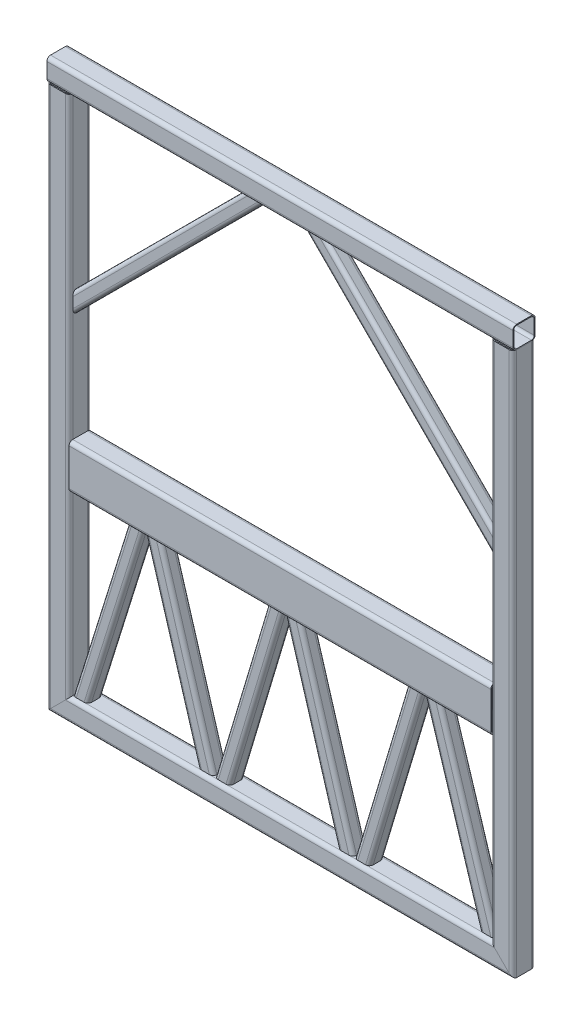
SolidWorks part; units mm, degrees
other "Weld Folder"
material "Plain Carbon Steel"
ref_plane "Front Plane" through (0, 0, 0) normal (0, 0, 1) x (1, 0, 0)
ref_plane "Top Plane" through (0, 0, 0) normal (0, 1, 0) x (1, 0, 0)
ref_plane "Right Plane" through (0, 0, 0) normal (1, 0, 0) x (0, 0, -1)
sketch "Sketch1" plane through (0, 0, 0) normal (0, 0, 1) x (1, 0, 0)
  line L0 (0, 0) -> (1524, 0)
  line L1 (1460.5, 38.1) -> (1270, 647.7)
  line L2 (311.15, 647.7) -> (493.7125, 38.1)
  line L3 (550.8625, 38.1) -> (733.425, 647.7)
  line L4 (1212.85, 647.7) -> (1030.2875, 38.1)
  line L5 (38.1, 1131.8875) -> (522.2875, 1131.8875) construction
  line L6 (254, 647.7) -> (63.5, 38.1)
  line L7 (0, 647.7) -> (1524, 647.7) construction
  line L8 (1524, 0) -> (1524, 1828.8)
  line L9 (1524, 1828.8) -> (0, 1828.8)
  line L10 (0, 1828.8) -> (0, 0)
  line L11 (38.1, 647.7) -> (38.1, 38.1) construction
  line L12 (38.1, 38.1) -> (1485.9, 38.1) construction
  line L13 (1485.9, 38.1) -> (1485.9, 647.7) construction
  line L14 (1485.9, 38.1) -> (1524, 38.1) construction
  line L15 (38.1, 38.1) -> (0, 38.1) construction
  line L16 (38.1, 38.1) -> (38.1, 0) construction
  line L17 (38.1, 38.1) -> (63.5, 38.1) construction
  line L18 (1485.9, 38.1) -> (1460.5, 38.1) construction
  line L19 (762, 647.7) -> (762, 0) construction
  line L20 (0, 723.9) -> (1524, 723.9)
  line L21 (790.575, 647.7) -> (973.1375, 38.1)
  line L22 (522.2875, 1131.8875) -> (1001.7125, 1131.8875) construction
  line L23 (1001.7125, 1131.8875) -> (1485.9, 1131.8875) construction
  line L24 (311.15, 647.7) -> (733.425, 647.7) construction
  line L25 (522.2875, 1131.8875) -> (522.2875, 647.7) construction
  line L26 (1001.7125, 1131.8875) -> (1001.7125, 647.7) construction
  dimension "D1" = 1524
  dimension "D2" = 76.2
  dimension "D3" = 1828.8
  dimension "D4" = 38.1
  dimension "D5" = 25.4
  dimension "D6" = 1016
  dimension "D7" = 723.9
  dimension "D8" = 57.15
  dimension "D9" = 57.15
  dimension "D10" = 57.15
  dimension "D11" = 57.15
  dimension "D12" = 57.15
ref_plane "Plane5" through (1524, 0, 0) normal (1, 0, 0) x (0, 0, -1)
other "Vertical Members"
ref_plane "Plane7" through (0, 1828.8, 0) normal (0, -1, 0) x (1, 0, 0)
sketch "Sketch111" plane through (0, 1828.8, 0) normal (0, -1, 0) x (1, 0, 0)
  line L0 (-25.4, -34.925) -> (25.4, -34.925)
  line L1 (-34.925, -25.4) -> (-34.925, 25.4)
  line L2 (25.4, 34.925) -> (-25.4, 34.925)
  line L3 (34.925, 25.4) -> (34.925, -25.4)
  line L4 (-25.4, -38.1) -> (25.4, -38.1)
  line L5 (-38.1, -25.4) -> (-38.1, 25.4)
  line L6 (25.4, 38.1) -> (-25.4, 38.1)
  line L7 (38.1, 25.4) -> (38.1, -25.4)
  line L8 (0, 0) -> (34.925, 0) construction
  line L9 (0, 0) -> (0, 34.925) construction
  arc A0 (38.1, 25.4) -> (25.4, 38.1) centre (25.4, 25.4) ccw
  arc A1 (25.4, -38.1) -> (38.1, -25.4) centre (25.4, -25.4) ccw
  arc A2 (-38.1, -25.4) -> (-25.4, -38.1) centre (-25.4, -25.4) ccw
  arc A3 (-25.4, 38.1) -> (-38.1, 25.4) centre (-25.4, 25.4) ccw
  arc A4 (-25.4, 34.925) -> (-34.925, 25.4) centre (-25.4, 25.4) ccw
  arc A5 (34.925, 25.4) -> (25.4, 34.925) centre (25.4, 25.4) ccw
  arc A6 (25.4, -34.925) -> (34.925, -25.4) centre (25.4, -25.4) ccw
  arc A7 (-34.925, -25.4) -> (-25.4, -34.925) centre (-25.4, -25.4) ccw
  point P3 (0, 38.1)
  point P4 (38.1, 0)
  point P5 (0, -38.1)
  point P6 (-38.1, 0)
  point P7 (-38.1, 38.1)
  point P8 (-38.1, -38.1)
  point P33 (0, 0)
  point P35 (38.1, -38.1)
  point P36 (38.1, 38.1)
  point P37 (0, 0)
  dimension "D1" = 12.7
  dimension "Thickness" = 3.175
  dimension "V_leg" = 76.2
other "Deck"
ref_plane "Plane10" through (0, 723.9, 0) normal (1, 0, 0) x (0, 1, 0)
sketch "Sketch115" plane through (0, 723.9, 0) normal (1, 0, 0) x (0, 1, 0)
  line L0 (-63.5, -33.3375) -> (63.5, -33.3375)
  line L1 (-71.4375, -25.4) -> (-71.4375, 25.4)
  line L2 (63.5, 33.3375) -> (-63.5, 33.3375)
  line L3 (71.4375, 25.4) -> (71.4375, -25.4)
  line L4 (-63.5, -38.1) -> (63.5, -38.1)
  line L5 (-76.2, -25.4) -> (-76.2, 25.4)
  line L6 (63.5, 38.1) -> (-63.5, 38.1)
  line L7 (76.2, 25.4) -> (76.2, -25.4)
  line L8 (0, 0) -> (76.2, 0) construction
  line L9 (0, 0) -> (0, 38.1) construction
  arc A0 (76.2, 25.4) -> (63.5, 38.1) centre (63.5, 25.4) ccw
  arc A1 (63.5, -38.1) -> (76.2, -25.4) centre (63.5, -25.4) ccw
  arc A2 (-76.2, -25.4) -> (-63.5, -38.1) centre (-63.5, -25.4) ccw
  arc A3 (-63.5, 38.1) -> (-76.2, 25.4) centre (-63.5, 25.4) ccw
  arc A4 (-63.5, 33.3375) -> (-71.4375, 25.4) centre (-63.5, 25.4) ccw
  arc A5 (71.4375, 25.4) -> (63.5, 33.3375) centre (63.5, 25.4) ccw
  arc A6 (63.5, -33.3375) -> (71.4375, -25.4) centre (63.5, -25.4) ccw
  arc A7 (-71.4375, -25.4) -> (-63.5, -33.3375) centre (-63.5, -25.4) ccw
  point P3 (0, -38.1)
  point P4 (-76.2, 0)
  point P5 (0, 0)
  point P6 (76.2, -38.1)
  point P7 (-76.2, -38.1)
  point P8 (-76.2, 38.1)
  point P33 (0, 0)
  point P35 (76.2, 38.1)
  point P36 (76.2, 0)
  point P37 (0, 38.1)
  dimension "D1" = 12.7
  dimension "Thickness" = 4.7625
  dimension "V_leg" = 76.2
  dimension "H_leg" = 152.4
other "Bottom"
ref_plane "Plane15" through (0, 0, 0) normal (1, 0, 0) x (0, 1, 0)
sketch "Sketch122" plane through (0, 0, 0) normal (1, 0, 0) x (0, 1, 0)
  line L0 (-25.4, -34.925) -> (25.4, -34.925)
  line L1 (-34.925, -25.4) -> (-34.925, 25.4)
  line L2 (25.4, 34.925) -> (-25.4, 34.925)
  line L3 (34.925, 25.4) -> (34.925, -25.4)
  line L4 (-25.4, -38.1) -> (25.4, -38.1)
  line L5 (-38.1, -25.4) -> (-38.1, 25.4)
  line L6 (25.4, 38.1) -> (-25.4, 38.1)
  line L7 (38.1, 25.4) -> (38.1, -25.4)
  line L8 (0, 0) -> (34.925, 0) construction
  line L9 (0, 0) -> (0, 34.925) construction
  arc A0 (38.1, 25.4) -> (25.4, 38.1) centre (25.4, 25.4) ccw
  arc A1 (25.4, -38.1) -> (38.1, -25.4) centre (25.4, -25.4) ccw
  arc A2 (-38.1, -25.4) -> (-25.4, -38.1) centre (-25.4, -25.4) ccw
  arc A3 (-25.4, 38.1) -> (-38.1, 25.4) centre (-25.4, 25.4) ccw
  arc A4 (-25.4, 34.925) -> (-34.925, 25.4) centre (-25.4, 25.4) ccw
  arc A5 (34.925, 25.4) -> (25.4, 34.925) centre (25.4, 25.4) ccw
  arc A6 (25.4, -34.925) -> (34.925, -25.4) centre (25.4, -25.4) ccw
  arc A7 (-34.925, -25.4) -> (-25.4, -34.925) centre (-25.4, -25.4) ccw
  point P3 (0, 38.1)
  point P4 (38.1, 0)
  point P5 (0, -38.1)
  point P6 (-38.1, 0)
  point P7 (-38.1, 38.1)
  point P8 (-38.1, -38.1)
  point P33 (0, 0)
  point P35 (38.1, -38.1)
  point P36 (38.1, 38.1)
  point P37 (0, 0)
  dimension "D1" = 12.7
  dimension "Thickness" = 3.175
  dimension "V_leg" = 76.2
other "Truss 1"
ref_plane "Plane9" through (254, 647.7, 0) normal (-0.2983, -0.9545, 0) x (0.9545, -0.2983, 0)
sketch "Sketch114" plane through (254, 647.7, 0) normal (-0.2983, -0.9545, 0) x (0.9545, -0.2983, 0)
  line L0 (-12.7, -22.225) -> (12.7, -22.225)
  line L1 (-22.225, -12.7) -> (-22.225, 12.7)
  line L2 (12.7, 22.225) -> (-12.7, 22.225)
  line L3 (22.225, 12.7) -> (22.225, -12.7)
  line L4 (-12.7, -25.4) -> (12.7, -25.4)
  line L5 (-25.4, -12.7) -> (-25.4, 12.7)
  line L6 (12.7, 25.4) -> (-12.7, 25.4)
  line L7 (25.4, 12.7) -> (25.4, -12.7)
  line L8 (0, 0) -> (22.225, 0) construction
  line L9 (0, 0) -> (0, 22.225) construction
  arc A0 (25.4, 12.7) -> (12.7, 25.4) centre (12.7, 12.7) ccw
  arc A1 (12.7, -25.4) -> (25.4, -12.7) centre (12.7, -12.7) ccw
  arc A2 (-25.4, -12.7) -> (-12.7, -25.4) centre (-12.7, -12.7) ccw
  arc A3 (-12.7, 25.4) -> (-25.4, 12.7) centre (-12.7, 12.7) ccw
  arc A4 (-12.7, 22.225) -> (-22.225, 12.7) centre (-12.7, 12.7) ccw
  arc A5 (22.225, 12.7) -> (12.7, 22.225) centre (12.7, 12.7) ccw
  arc A6 (12.7, -22.225) -> (22.225, -12.7) centre (12.7, -12.7) ccw
  arc A7 (-22.225, -12.7) -> (-12.7, -22.225) centre (-12.7, -12.7) ccw
  point P3 (0, 25.4)
  point P4 (25.4, 0)
  point P5 (0, -25.4)
  point P6 (-25.4, 0)
  point P7 (-25.4, 25.4)
  point P8 (-25.4, -25.4)
  point P33 (0, 0)
  point P35 (25.4, -25.4)
  point P36 (25.4, 25.4)
  point P37 (0, 0)
  dimension "D1" = 12.7
  dimension "Thickness" = 3.175
  dimension "V_leg" = 50.8
other "Truss 2"
ref_plane "Plane12" through (311.15, 647.7, 0) normal (0.2869, -0.958, 0) x (0.958, 0.2869, 0)
sketch "Sketch118" plane through (311.15, 647.7, 0) normal (0.2869, -0.958, 0) x (0.958, 0.2869, 0)
  line L0 (-12.7, -22.225) -> (12.7, -22.225)
  line L1 (-22.225, -12.7) -> (-22.225, 12.7)
  line L2 (12.7, 22.225) -> (-12.7, 22.225)
  line L3 (22.225, 12.7) -> (22.225, -12.7)
  line L4 (-12.7, -25.4) -> (12.7, -25.4)
  line L5 (-25.4, -12.7) -> (-25.4, 12.7)
  line L6 (12.7, 25.4) -> (-12.7, 25.4)
  line L7 (25.4, 12.7) -> (25.4, -12.7)
  line L8 (0, 0) -> (22.225, 0) construction
  line L9 (0, 0) -> (0, 22.225) construction
  arc A0 (25.4, 12.7) -> (12.7, 25.4) centre (12.7, 12.7) ccw
  arc A1 (12.7, -25.4) -> (25.4, -12.7) centre (12.7, -12.7) ccw
  arc A2 (-25.4, -12.7) -> (-12.7, -25.4) centre (-12.7, -12.7) ccw
  arc A3 (-12.7, 25.4) -> (-25.4, 12.7) centre (-12.7, 12.7) ccw
  arc A4 (-12.7, 22.225) -> (-22.225, 12.7) centre (-12.7, 12.7) ccw
  arc A5 (22.225, 12.7) -> (12.7, 22.225) centre (12.7, 12.7) ccw
  arc A6 (12.7, -22.225) -> (22.225, -12.7) centre (12.7, -12.7) ccw
  arc A7 (-22.225, -12.7) -> (-12.7, -22.225) centre (-12.7, -12.7) ccw
  point P3 (0, 25.4)
  point P4 (25.4, 0)
  point P5 (0, -25.4)
  point P6 (-25.4, 0)
  point P7 (-25.4, 25.4)
  point P8 (-25.4, -25.4)
  point P33 (0, 0)
  point P35 (25.4, -25.4)
  point P36 (25.4, 25.4)
  point P37 (0, 0)
  dimension "D1" = 12.7
  dimension "Thickness" = 3.175
  dimension "V_leg" = 50.8
other "Truss 3"
ref_plane "Plane13" through (550.8625, 38.1, 0) normal (0.2869, 0.958, 0) x (-0.958, 0.2869, 0)
sketch "Sketch119" plane through (550.8625, 38.1, 0) normal (0.2869, 0.958, 0) x (-0.958, 0.2869, 0)
  line L0 (-12.7, -22.225) -> (12.7, -22.225)
  line L1 (-22.225, -12.7) -> (-22.225, 12.7)
  line L2 (12.7, 22.225) -> (-12.7, 22.225)
  line L3 (22.225, 12.7) -> (22.225, -12.7)
  line L4 (-12.7, -25.4) -> (12.7, -25.4)
  line L5 (-25.4, -12.7) -> (-25.4, 12.7)
  line L6 (12.7, 25.4) -> (-12.7, 25.4)
  line L7 (25.4, 12.7) -> (25.4, -12.7)
  line L8 (0, 0) -> (22.225, 0) construction
  line L9 (0, 0) -> (0, 22.225) construction
  arc A0 (25.4, 12.7) -> (12.7, 25.4) centre (12.7, 12.7) ccw
  arc A1 (12.7, -25.4) -> (25.4, -12.7) centre (12.7, -12.7) ccw
  arc A2 (-25.4, -12.7) -> (-12.7, -25.4) centre (-12.7, -12.7) ccw
  arc A3 (-12.7, 25.4) -> (-25.4, 12.7) centre (-12.7, 12.7) ccw
  arc A4 (-12.7, 22.225) -> (-22.225, 12.7) centre (-12.7, 12.7) ccw
  arc A5 (22.225, 12.7) -> (12.7, 22.225) centre (12.7, 12.7) ccw
  arc A6 (12.7, -22.225) -> (22.225, -12.7) centre (12.7, -12.7) ccw
  arc A7 (-22.225, -12.7) -> (-12.7, -22.225) centre (-12.7, -12.7) ccw
  point P3 (0, 25.4)
  point P4 (25.4, 0)
  point P5 (0, -25.4)
  point P6 (-25.4, 0)
  point P7 (-25.4, 25.4)
  point P8 (-25.4, -25.4)
  point P33 (0, 0)
  point P35 (25.4, -25.4)
  point P36 (25.4, 25.4)
  point P37 (0, 0)
  dimension "D1" = 12.7
  dimension "Thickness" = 3.175
  dimension "V_leg" = 50.8
other "Deck trim"
other "Truss Trim"
other "Bottom miter 1"
other "Bottom miter 2"
sketch "Sketch126" plane through (0, 0, 0) normal (0, 0, 1) x (1, 0, 0)
  line L0 (0, 1828.8) -> (1524, 1828.8) construction
  line L1 (25.4, 1828.8) -> (-25.4, 1828.8) construction
  line L2 (1549.4, 1828.8) -> (1498.6, 1828.8) construction
  line L3 (0, 1828.8) -> (0, 1866.9) construction
  line L4 (0, 1866.9) -> (1524, 1866.9)
  line L5 (1524, 1866.9) -> (1524, 1828.8) construction
  dimension "D1" = 38.1
other "Structural Member1"
ref_plane "Plane18" through (0, 1866.9, 0) normal (1, 0, 0) x (0, 1, 0)
sketch "Sketch128" plane through (0, 1866.9, 0) normal (1, 0, 0) x (0, 1, 0)
  line L0 (-25.4, -34.925) -> (25.4, -34.925)
  line L1 (-34.925, -25.4) -> (-34.925, 25.4)
  line L2 (25.4, 34.925) -> (-25.4, 34.925)
  line L3 (34.925, 25.4) -> (34.925, -25.4)
  line L4 (-25.4, -38.1) -> (25.4, -38.1)
  line L5 (-38.1, -25.4) -> (-38.1, 25.4)
  line L6 (25.4, 38.1) -> (-25.4, 38.1)
  line L7 (38.1, 25.4) -> (38.1, -25.4)
  line L8 (0, 0) -> (34.925, 0) construction
  line L9 (0, 0) -> (0, 34.925) construction
  arc A0 (38.1, 25.4) -> (25.4, 38.1) centre (25.4, 25.4) ccw
  arc A1 (25.4, -38.1) -> (38.1, -25.4) centre (25.4, -25.4) ccw
  arc A2 (-38.1, -25.4) -> (-25.4, -38.1) centre (-25.4, -25.4) ccw
  arc A3 (-25.4, 38.1) -> (-38.1, 25.4) centre (-25.4, 25.4) ccw
  arc A4 (-25.4, 34.925) -> (-34.925, 25.4) centre (-25.4, 25.4) ccw
  arc A5 (34.925, 25.4) -> (25.4, 34.925) centre (25.4, 25.4) ccw
  arc A6 (25.4, -34.925) -> (34.925, -25.4) centre (25.4, -25.4) ccw
  arc A7 (-34.925, -25.4) -> (-25.4, -34.925) centre (-25.4, -25.4) ccw
  point P3 (0, 38.1)
  point P4 (38.1, 0)
  point P5 (0, -38.1)
  point P6 (-38.1, 0)
  point P7 (-38.1, 38.1)
  point P8 (-38.1, -38.1)
  point P33 (0, 0)
  point P35 (38.1, -38.1)
  point P36 (38.1, 38.1)
  point P37 (0, 0)
  dimension "D1" = 12.7
  dimension "Thickness" = 3.175
  dimension "V_leg" = 76.2
other "Trim/Extend1"
other "Trim/Extend2"
sketch "Sketch130" plane through (0, 0, 0) normal (0, 0, 1) x (1, 0, 0)
  line L0 (660.4, 1828.8) -> (38.1, 1206.5)
  line L1 (1562.1, 1828.8) -> (-38.1, 1828.8) construction
  line L3 (863.6, 1828.8) -> (1485.9, 1206.5)
  line L4 (38.1, 38.1) -> (38.1, 1828.8) construction
  line L5 (1485.9, 38.1) -> (1485.9, 1828.8) construction
  dimension "D1" = 203.2
  dimension "D2" = 45
other "Structural Member2"
ref_plane "Plane19" through (660.4, 1828.8, 0) normal (-0.7071, -0.7071, 0) x (0.7071, -0.7071, 0)
sketch "Sketch131" plane through (660.4, 1828.8, 0) normal (-0.7071, -0.7071, 0) x (0.7071, -0.7071, 0)
  line L0 (-12.7, -19.05) -> (12.7, -19.05)
  line L1 (-19.05, -12.7) -> (-19.05, 12.7)
  line L2 (12.7, 19.05) -> (-12.7, 19.05)
  line L3 (19.05, 12.7) -> (19.05, -12.7)
  line L4 (-12.7, -25.4) -> (12.7, -25.4)
  line L5 (-25.4, -12.7) -> (-25.4, 12.7)
  line L6 (12.7, 25.4) -> (-12.7, 25.4)
  line L7 (25.4, 12.7) -> (25.4, -12.7)
  line L8 (0, 0) -> (19.05, 0) construction
  line L9 (0, 0) -> (0, 19.05) construction
  arc A0 (25.4, 12.7) -> (12.7, 25.4) centre (12.7, 12.7) ccw
  arc A1 (12.7, -25.4) -> (25.4, -12.7) centre (12.7, -12.7) ccw
  arc A2 (-25.4, -12.7) -> (-12.7, -25.4) centre (-12.7, -12.7) ccw
  arc A3 (-12.7, 25.4) -> (-25.4, 12.7) centre (-12.7, 12.7) ccw
  arc A4 (-12.7, 19.05) -> (-19.05, 12.7) centre (-12.7, 12.7) ccw
  arc A5 (19.05, 12.7) -> (12.7, 19.05) centre (12.7, 12.7) ccw
  arc A6 (12.7, -19.05) -> (19.05, -12.7) centre (12.7, -12.7) ccw
  arc A7 (-19.05, -12.7) -> (-12.7, -19.05) centre (-12.7, -12.7) ccw
  point P3 (0, 25.4)
  point P4 (25.4, 0)
  point P5 (0, -25.4)
  point P6 (-25.4, 0)
  point P7 (-25.4, 25.4)
  point P8 (-25.4, -25.4)
  point P33 (0, 0)
  point P35 (25.4, -25.4)
  point P36 (25.4, 25.4)
  point P37 (0, 0)
  dimension "D1" = 12.7
  dimension "Thickness" = 6.35
  dimension "V_leg" = 50.8
other "Trim/Extend3"
other "Trim/Extend4"
